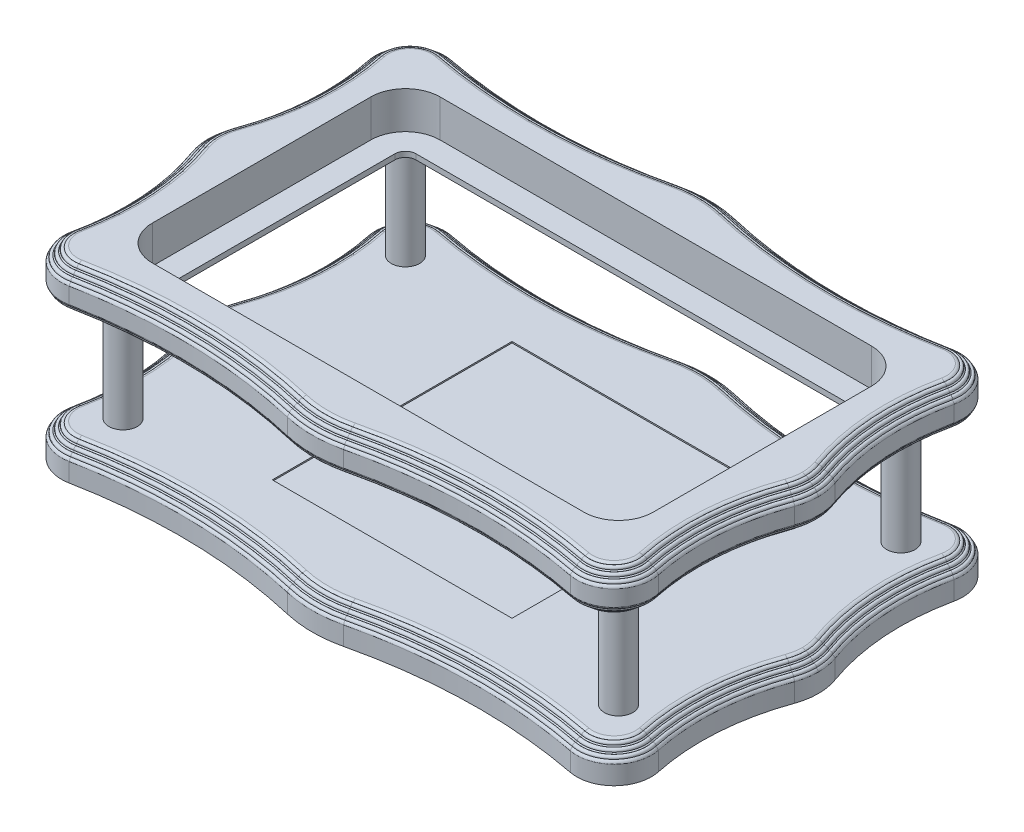
SolidWorks part; units mm, degrees
ref_plane "Front Plane" through (0, 0, 0) normal (0, 0, 1) x (1, 0, 0)
ref_plane "Top Plane" through (0, 0, 0) normal (0, 1, 0) x (1, 0, 0)
ref_plane "Right Plane" through (0, 0, 0) normal (1, 0, 0) x (0, 0, -1)
sketch "Sketch1" plane through (0, 0, 0) normal (0, 1, 0) x (1, 0, 0)
  line L0 (0, 22.5) -> (0, 30.5) construction
  line L1 (50.5, -30.5) -> (-50.5, -30.5) construction
  line L2 (50.5, -30.5) -> (50.5, 30.5) construction
  line L3 (50.5, 30.5) -> (-50.5, 30.5) construction
  line L4 (-50.5, -30.5) -> (-50.5, 30.5) construction
  line L5 (50.5, -30.5) -> (-50.5, 30.5) construction
  line L6 (50.5, 30.5) -> (-50.5, -30.5) construction
  line L7 (-42.5, 22.5) -> (42.5, 22.5) construction
  line L8 (-42.5, 22.5) -> (-42.5, -22.5) construction
  line L9 (-42.5, -22.5) -> (42.5, -22.5) construction
  line L10 (42.5, 22.5) -> (42.5, -22.5) construction
  line L11 (-42.5, 22.5) -> (42.5, -22.5) construction
  line L12 (-42.5, -22.5) -> (42.5, 22.5) construction
  line L13 (42.5, 0) -> (50.5, 0) construction
  line L14 (57.5, 0) -> (50.5, 0) construction
  line L19 (-46.5, 26.5) -> (46.5, 26.5) construction
  line L20 (-46.5, 26.5) -> (-46.5, -26.5) construction
  line L21 (-46.5, -26.5) -> (46.5, -26.5) construction
  line L22 (46.5, 26.5) -> (46.5, -26.5) construction
  line L23 (-46.5, 26.5) -> (46.5, -26.5) construction
  line L24 (-46.5, -26.5) -> (46.5, 26.5) construction
  line L25 (-57.5, 37.5) -> (57.5, 37.5)
  line L26 (-57.5, 37.5) -> (-57.5, -37.5)
  line L27 (-57.5, -37.5) -> (57.5, -37.5)
  line L28 (57.5, 37.5) -> (57.5, -37.5)
  line L29 (-57.5, 37.5) -> (57.5, -37.5) construction
  line L30 (-57.5, -37.5) -> (57.5, 37.5) construction
  line L31 (0, 30.5) -> (0, 37.5) construction
  circle A0 centre (46.5, 26.5) radius 2.6667 construction
  circle A1 centre (-46.5, 26.5) radius 2.6667 construction
  circle A2 centre (46.5, -26.5) radius 2.6667 construction
  circle A3 centre (-46.5, -26.5) radius 2.6667 construction
  point P0 (0, 0)
  point P6 (0, 0)
  point P17 (0, 0)
  point P24 (0, 0)
  point P29 (46.5, 0)
  point P30 (0, 26.5)
  dimension "D5" = 5.3333
  dimension "D1" = 85
  dimension "D2" = 45
  dimension "D3" = 8
  dimension "D4" = 7
extrude "Base" add sketch "Sketch1" along normal blind 6
sketch "Path" plane through (0, 6, 0) normal (0, 1, 0) x (1, 0, 0)
  line L0 (51.25, 0) -> (50.5, 0) construction
  line L1 (28.0361, 31.25) -> (28.0361, 30.5) construction
  line L2 (-4.5909, 34.5) -> (4.5909, 34.5) construction
  line L3 (-54.5, 4.5909) -> (-54.5, -4.5909) construction
  line L4 (-50.5, -30.5) -> (-50.5, 30.5) construction
  line L5 (-50.5, 30.5) -> (50.5, 30.5) construction
  line L6 (-57.5, 37.5) -> (-57.5, -37.5) construction
  line L7 (57.5, 37.5) -> (-57.5, 37.5) construction
  line L8 (0, 34.5) -> (0, 37.5) construction
  line L9 (-54.5, 0) -> (-57.5, 0) construction
  line L10 (0, 0) -> (-50.5, 30.5) construction
  line L11 (-51.25, 31.25) -> (-51.25, -31.25) construction
  line L12 (-51.25, 31.25) -> (51.25, 31.25) construction
  line L13 (-50.5, 0) -> (-41.3182, 0) construction
  line L14 (-41.3182, 0) -> (-32.1364, 0) construction
  line L15 (-32.1364, 0) -> (-22.9545, 0) construction
  line L16 (-22.9545, 0) -> (-13.7727, 0) construction
  line L17 (-13.7727, 0) -> (-4.5909, 0) construction
  line L18 (-4.5909, 0) -> (4.5909, 0) construction
  line L19 (-4.5909, 33.9678) -> (4.5909, 33.9678) construction
  line L20 (-28.0361, 30.5) -> (-28.0361, 24.9545) construction
  line L21 (-28.0361, 24.9545) -> (-28.0361, 19.4091) construction
  line L22 (-28.0361, 19.4091) -> (-28.0361, 13.8636) construction
  line L23 (-28.0361, 13.8636) -> (-28.0361, 8.3182) construction
  line L24 (-28.0361, 8.3182) -> (-28.0361, 2.7727) construction
  line L25 (-28.0361, 2.7727) -> (-28.0361, -2.7727) construction
  line L26 (-54.0165, 2.7727) -> (-54.0165, -2.7727) construction
  line L27 (0, 37.5) -> (0, 46.6818) construction
  line L28 (-57.5, 0) -> (-66.6818, 0) construction
  line L29 (-28.0361, 31.25) -> (-28.0361, 30.5) construction
  line L30 (-51.25, 0) -> (-50.5, 0) construction
  line L31 (54.0165, 2.7727) -> (54.0165, -2.7727) construction
  line L32 (28.0361, 2.7727) -> (28.0361, -2.7727) construction
  line L33 (28.0361, 8.3182) -> (28.0361, 2.7727) construction
  line L34 (28.0361, 13.8636) -> (28.0361, 8.3182) construction
  line L35 (28.0361, 19.4091) -> (28.0361, 13.8636) construction
  line L36 (28.0361, 24.9545) -> (28.0361, 19.4091) construction
  line L37 (28.0361, 30.5) -> (28.0361, 24.9545) construction
  line L38 (13.7727, 0) -> (4.5909, 0) construction
  line L39 (22.9545, 0) -> (13.7727, 0) construction
  line L40 (32.1364, 0) -> (22.9545, 0) construction
  line L41 (41.3182, 0) -> (32.1364, 0) construction
  line L42 (50.5, 0) -> (41.3182, 0) construction
  line L43 (51.25, 31.25) -> (51.25, -31.25) construction
  line L44 (0, 0) -> (50.5, 30.5) construction
  line L45 (54.5, 0) -> (57.5, 0) construction
  line L46 (50.5, -30.5) -> (50.5, 30.5) construction
  line L47 (54.5, 4.5909) -> (54.5, -4.5909) construction
  line L48 (0, 0) -> (50.5, -30.5) construction
  line L49 (50.5, 0) -> (41.3182, 0) construction
  line L50 (41.3182, 0) -> (32.1364, 0) construction
  line L51 (32.1364, 0) -> (22.9545, 0) construction
  line L52 (22.9545, 0) -> (13.7727, 0) construction
  line L53 (13.7727, 0) -> (4.5909, 0) construction
  line L54 (28.0361, -30.5) -> (28.0361, -24.9545) construction
  line L55 (28.0361, -24.9545) -> (28.0361, -19.4091) construction
  line L56 (28.0361, -19.4091) -> (28.0361, -13.8636) construction
  line L57 (28.0361, -13.8636) -> (28.0361, -8.3182) construction
  line L58 (28.0361, -8.3182) -> (28.0361, -2.7727) construction
  line L59 (-51.25, 0) -> (-50.5, 0) construction
  line L60 (-28.0361, -31.25) -> (-28.0361, -30.5) construction
  line L61 (0, -37.5) -> (0, -46.6818) construction
  line L62 (-28.0361, -8.3182) -> (-28.0361, -2.7727) construction
  line L63 (-28.0361, -13.8636) -> (-28.0361, -8.3182) construction
  line L64 (-28.0361, -19.4091) -> (-28.0361, -13.8636) construction
  line L65 (-28.0361, -24.9545) -> (-28.0361, -19.4091) construction
  line L66 (-28.0361, -30.5) -> (-28.0361, -24.9545) construction
  line L67 (-4.5909, -33.9678) -> (4.5909, -33.9678) construction
  line L68 (-4.5909, 0) -> (4.5909, 0) construction
  line L69 (-13.7727, 0) -> (-4.5909, 0) construction
  line L70 (-22.9545, 0) -> (-13.7727, 0) construction
  line L71 (-32.1364, 0) -> (-22.9545, 0) construction
  line L72 (-41.3182, 0) -> (-32.1364, 0) construction
  line L73 (-50.5, 0) -> (-41.3182, 0) construction
  line L74 (-51.25, -31.25) -> (51.25, -31.25) construction
  line L75 (0, 0) -> (-50.5, -30.5) construction
  line L76 (0, -34.5) -> (0, -37.5) construction
  line L77 (-50.5, -30.5) -> (50.5, -30.5) construction
  line L78 (-4.5909, -34.5) -> (4.5909, -34.5) construction
  line L79 (28.0361, -31.25) -> (28.0361, -30.5) construction
  line L80 (51.25, 0) -> (50.5, 0) construction
  arc A0 (4.5909, 33.9678) -> (-4.5909, 33.9678) centre (0, 14.4322) ccw
  arc A1 (-54.0165, -2.7727) -> (-54.0165, 2.7727) centre (-46.3077, 0) cw
  circle A2 centre (-48.36, 29.2075) radius 4 construction
  arc A3 (-54.0165, 2.7727) -> (-52.2727, 28.3765) centre (-98.1256, 18.6381) ccw
  arc A4 (-4.5909, 33.9678) -> (-47.5966, 33.134) centre (-28.0361, 133.734) cw
  arc A5 (-52.2727, 28.3765) -> (-47.5966, 33.134) centre (-48.36, 29.2075) cw
  circle A6 centre (48.36, 29.2075) radius 4 construction
  arc A7 (52.2727, 28.3765) -> (47.5966, 33.134) centre (48.36, 29.2075) ccw
  arc A8 (4.5909, 33.9678) -> (47.5966, 33.134) centre (28.0361, 133.734) ccw
  arc A9 (54.0165, 2.7727) -> (52.2727, 28.3765) centre (98.1256, 18.6381) cw
  arc A10 (54.0165, -2.7727) -> (54.0165, 2.7727) centre (46.3077, 0) ccw
  circle A11 centre (48.36, -29.2075) radius 4 construction
  circle A12 centre (-48.36, -29.2075) radius 4 construction
  arc A13 (54.0165, -2.7727) -> (52.2727, -28.3765) centre (98.1256, -18.6381) ccw
  arc A14 (4.5909, -33.9678) -> (47.5966, -33.134) centre (28.0361, -133.734) cw
  arc A15 (52.2727, -28.3765) -> (47.5966, -33.134) centre (48.36, -29.2075) cw
  arc A16 (-52.2727, -28.3765) -> (-47.5966, -33.134) centre (-48.36, -29.2075) ccw
  arc A17 (-4.5909, -33.9678) -> (-47.5966, -33.134) centre (-28.0361, -133.734) ccw
  arc A18 (-54.0165, -2.7727) -> (-52.2727, -28.3765) centre (-98.1256, -18.6381) cw
  arc A19 (4.5909, -33.9678) -> (-4.5909, -33.9678) centre (0, -14.4322) cw
  point P37 (-50.5, 0)
  point P46 (0, 0)
  point P72 (0, 33.9678)
  point P73 (0, 0)
  point P78 (0, 31.25)
  point P82 (0, 30.5)
  point P96 (50.5, 0)
  point P97 (51.25, 0)
  point P109 (28.0361, 0)
  point P110 (54.0165, 0)
  point P117 (-54.0165, 0)
  point P118 (-28.0361, 0)
  point P130 (-51.25, 0)
  point P132 (-50.5, 0)
  point P146 (0, -30.5)
  point P147 (0, -31.25)
  point P148 (0, 0)
  point P149 (0, -33.9678)
  dimension "D5" = 8
  dimension "D1" = 7
  dimension "D2" = 7
  dimension "D3" = 3
  dimension "D4" = 2.5
  dimension "D7" = 0.75
sketch "Profile" plane through (0, 0, 0) normal (0, 0, 1) x (1, 0, 0)
  line L0 (54.5, 6) -> (57.5, 6)
  line L1 (57.5, 6) -> (57.5, 3.5) construction
  line L2 (57.5, 6) -> (55.25, 5.375) construction
  line L3 (57.5, 6) -> (56, 4.75) construction
  line L4 (57.5, 6) -> (56.75, 4.125) construction
  line L5 (55.25, 5.375) -> (54.5, 6) construction
  line L6 (55.25, 5.375) -> (56, 4.75) construction
  line L7 (56, 4.75) -> (56.75, 4.125) construction
  line L8 (56.75, 4.125) -> (57.5, 3.5) construction
  line L9 (56, 4.75) -> (57.5, 4.75) construction
  line L10 (56.75, 4.125) -> (57.5, 4.125) construction
  line L11 (55.25, 5.375) -> (57.5, 5.375) construction
  line L12 (57.5, 6) -> (67.5, 8)
  line L13 (67.5, 8) -> (67.5, 3.5)
  line L15 (57.5, 3.5) -> (57.5, -4.5)
  line L16 (57.5, -4.5) -> (67.5, -4.5)
  line L17 (57.5, 3.5) -> (67.5, 3.5) construction
  line L18 (67.5, -4.5) -> (67.5, 3.5)
  circle A0 centre (55.25, 5.375) radius 0.39 construction
  circle A1 centre (56, 4.75) radius 0.39 construction
  circle A2 centre (56.75, 4.125) radius 0.39 construction
  arc A3 (56.75, 4.125) -> (57.5, 3.5) centre (56.75, 3.3625) cw construction
  arc A4 (56, 4.75) -> (56.75, 4.125) centre (56, 3.9875) cw construction
  arc A5 (55.25, 5.375) -> (56, 4.75) centre (55.25, 4.6125) cw construction
  arc A6 (54.5, 6) -> (55.25, 5.375) centre (54.5, 5.2375) cw construction
  arc A7 (54.5, 6) -> (55.0839, 5.7279) centre (54.5, 5.2375) cw
  arc A8 (55.0839, 5.7279) -> (55.627, 5.2753) centre (55.25, 5.375) cw
  arc A9 (55.627, 5.2753) -> (55.8339, 5.1029) centre (55.25, 4.6125) cw
  arc A10 (55.8339, 5.1029) -> (56.377, 4.6503) centre (56, 4.75) cw
  arc A11 (56.377, 4.6503) -> (56.5839, 4.4779) centre (56, 3.9875) cw
  arc A12 (56.5839, 4.4779) -> (57.127, 4.0253) centre (56.75, 4.125) cw
  arc A13 (57.127, 4.0253) -> (57.5, 3.5) centre (56.75, 3.3625) cw
  dimension "D3" = 0.78
  dimension "D1" = 3
  dimension "D2" = 2.5
  dimension "D4" = 10
  dimension "D5" = 8
sweep "Sweep Cut" cut profiles "Profile" path "Path"
sketch "Sketch4" plane through (0, 6, 0) normal (0, 1, 0) x (1, 0, 0)
  circle A0 centre (-46.5, -26.5) radius 2.6667 construction
  circle A1 centre (46.5, -26.5) radius 2.6667 construction
  circle A2 centre (46.5, 26.5) radius 2.6667 construction
  circle A3 centre (-46.5, 26.5) radius 2.6667 construction
  circle A4 centre (-46.5, -26.5) radius 2.6667
  circle A5 centre (46.5, -26.5) radius 2.6667
  circle A6 centre (46.5, 26.5) radius 2.6667
  circle A7 centre (-46.5, 26.5) radius 2.6667
extrude "Support Posts" add sketch "Sketch4" along normal blind 20.5
sketch "Sketch5" plane through (0, 6, 0) normal (0, 1, 0) x (1, 0, 0)
  line L1 (22.5, -22.5) -> (-22.5, -22.5)
  line L2 (22.5, -22.5) -> (22.5, 22.5)
  line L3 (22.5, 22.5) -> (-22.5, 22.5)
  line L4 (-22.5, -22.5) -> (-22.5, 22.5)
  line L5 (22.5, -22.5) -> (-22.5, 22.5) construction
  line L6 (22.5, 22.5) -> (-22.5, -22.5) construction
  point P0 (0, 0)
  dimension "D1" = 45
extrude "Pyramid Base Cut" cut sketch "Sketch5" against normal blind 0.25
sketch "Sketch6" plane through (0, 26.5, 0) normal (0, 1, 0) x (1, 0, 0)
  line L0 (-57.5, 37.5) -> (57.5, 37.5) construction
  line L1 (57.5, 37.5) -> (57.5, -37.5) construction
  line L2 (-57.5, -37.5) -> (57.5, -37.5) construction
  line L3 (-57.5, 37.5) -> (-57.5, -37.5) construction
  line L4 (-57.5, 37.5) -> (57.5, 37.5)
  line L5 (57.5, 37.5) -> (57.5, -37.5)
  line L6 (-57.5, -37.5) -> (57.5, -37.5)
  line L7 (-57.5, 37.5) -> (-57.5, -37.5)
extrude "Boss-Extrude2" add sketch "Sketch6" along normal blind 8
sketch "Path 2" plane through (0, 26.5, 0) normal (0, -1, 0) x (1, 0, 0)
  arc A16 (52.2727, 28.3765) -> (54.0165, 2.7727) centre (98.1256, 18.6381) ccw
  arc A17 (54.0165, -2.7727) -> (54.0165, 2.7727) centre (46.3077, 0) ccw
  arc A18 (54.0165, -2.7727) -> (52.2727, -28.3765) centre (98.1256, -18.6381) ccw
  arc A19 (47.5966, -33.134) -> (52.2727, -28.3765) centre (48.36, -29.2075) ccw
  arc A20 (47.5966, -33.134) -> (4.5909, -33.9678) centre (28.0361, -133.734) ccw
  arc A21 (-4.5909, -33.9678) -> (4.5909, -33.9678) centre (0, -14.4322) ccw
  arc A22 (-4.5909, -33.9678) -> (-47.5966, -33.134) centre (-28.0361, -133.734) ccw
  arc A23 (-52.2727, -28.3765) -> (-47.5966, -33.134) centre (-48.36, -29.2075) ccw
  arc A24 (-52.2727, -28.3765) -> (-54.0165, -2.7727) centre (-98.1256, -18.6381) ccw
  arc A25 (-54.0165, 2.7727) -> (-54.0165, -2.7727) centre (-46.3077, 0) ccw
  arc A26 (-54.0165, 2.7727) -> (-52.2727, 28.3765) centre (-98.1256, 18.6381) ccw
  arc A27 (-47.5966, 33.134) -> (-52.2727, 28.3765) centre (-48.36, 29.2075) ccw
  arc A28 (-47.5966, 33.134) -> (-4.5909, 33.9678) centre (-28.0361, 133.734) ccw
  arc A29 (4.5909, 33.9678) -> (-4.5909, 33.9678) centre (0, 14.4322) ccw
  arc A30 (4.5909, 33.9678) -> (47.5966, 33.134) centre (28.0361, 133.734) ccw
  arc A31 (52.2727, 28.3765) -> (47.5966, 33.134) centre (48.36, 29.2075) ccw
  arc A32 (52.2727, 28.3765) -> (54.0165, 2.7727) centre (98.1256, 18.6381) ccw
  arc A33 (54.0165, -2.7727) -> (54.0165, 2.7727) centre (46.3077, 0) ccw
  arc A34 (54.0165, -2.7727) -> (52.2727, -28.3765) centre (98.1256, -18.6381) ccw
  arc A35 (47.5966, -33.134) -> (52.2727, -28.3765) centre (48.36, -29.2075) ccw
  arc A36 (47.5966, -33.134) -> (4.5909, -33.9678) centre (28.0361, -133.734) ccw
  arc A37 (-4.5909, -33.9678) -> (4.5909, -33.9678) centre (0, -14.4322) ccw
  arc A38 (-4.5909, -33.9678) -> (-47.5966, -33.134) centre (-28.0361, -133.734) ccw
  arc A39 (-52.2727, -28.3765) -> (-47.5966, -33.134) centre (-48.36, -29.2075) ccw
  arc A40 (-52.2727, -28.3765) -> (-54.0165, -2.7727) centre (-98.1256, -18.6381) ccw
  arc A41 (-54.0165, 2.7727) -> (-54.0165, -2.7727) centre (-46.3077, 0) ccw
  arc A42 (-54.0165, 2.7727) -> (-52.2727, 28.3765) centre (-98.1256, 18.6381) ccw
  arc A43 (-47.5966, 33.134) -> (-52.2727, 28.3765) centre (-48.36, 29.2075) ccw
  arc A44 (-47.5966, 33.134) -> (-4.5909, 33.9678) centre (-28.0361, 133.734) ccw
  arc A45 (4.5909, 33.9678) -> (-4.5909, 33.9678) centre (0, 14.4322) ccw
  arc A46 (4.5909, 33.9678) -> (47.5966, 33.134) centre (28.0361, 133.734) ccw
  arc A47 (52.2727, 28.3765) -> (47.5966, 33.134) centre (48.36, 29.2075) ccw
  dimension "D1" = 0
sketch "Profile 2" plane through (0, 0, 0) normal (0, 0, 1) x (1, 0, 0)
  line L0 (54.5, 34.5) -> (57.5, 34.5)
  line L1 (57.5, 34.5) -> (57.5, 32) construction
  line L2 (57.5, 34.5) -> (55.25, 33.875) construction
  line L3 (57.5, 34.5) -> (56, 33.25) construction
  line L4 (57.5, 34.5) -> (56.75, 32.625) construction
  line L5 (55.25, 33.875) -> (54.5, 34.5) construction
  line L6 (55.25, 33.875) -> (56, 33.25) construction
  line L7 (56, 33.25) -> (56.75, 32.625) construction
  line L8 (56.75, 32.625) -> (57.5, 32) construction
  line L9 (56, 33.25) -> (57.5, 33.25) construction
  line L10 (56.75, 32.625) -> (57.5, 32.625) construction
  line L11 (55.25, 33.875) -> (57.5, 33.875) construction
  line L12 (57.5, 34.5) -> (67.5, 34.5)
  line L13 (67.5, 34.5) -> (67.5, 32)
  line L14 (57.5, 32) -> (57.5, 29)
  line L15 (57.5, 30.5) -> (67.5, 30.5) construction
  line L16 (57.5, 32) -> (67.5, 32) construction
  line L17 (67.5, 29) -> (67.5, 32)
  line L18 (67.5, 30.5) -> (70, 30.5) construction
  line L19 (57.5, 29) -> (67.5, 29) construction
  line L20 (55.25, 27.125) -> (57.5, 27.125) construction
  line L21 (56.75, 28.375) -> (57.5, 28.375) construction
  line L22 (56, 27.75) -> (57.5, 27.75) construction
  line L23 (56.75, 28.375) -> (57.5, 29) construction
  line L24 (56, 27.75) -> (56.75, 28.375) construction
  line L25 (55.25, 27.125) -> (56, 27.75) construction
  line L26 (55.25, 27.125) -> (54.5, 26.5) construction
  line L27 (57.5, 26.5) -> (56.75, 28.375) construction
  line L28 (57.5, 26.5) -> (56, 27.75) construction
  line L29 (57.5, 26.5) -> (55.25, 27.125) construction
  line L30 (57.5, 26.5) -> (57.5, 29) construction
  line L31 (67.5, 26.5) -> (67.5, 29)
  line L32 (57.5, 26.5) -> (67.5, 26.5)
  line L33 (54.5, 26.5) -> (57.5, 26.5)
  line L39 (-57.5, 34.5) -> (57.5, 34.5) construction
  circle A0 centre (55.25, 33.875) radius 0.39 construction
  circle A1 centre (56, 33.25) radius 0.39 construction
  circle A2 centre (56.75, 32.625) radius 0.39 construction
  arc A3 (56.75, 32.625) -> (57.5, 32) centre (56.75, 31.8625) cw construction
  arc A4 (56, 33.25) -> (56.75, 32.625) centre (56, 32.4875) cw construction
  arc A5 (55.25, 33.875) -> (56, 33.25) centre (55.25, 33.1125) cw construction
  arc A6 (54.5, 34.5) -> (55.25, 33.875) centre (54.5, 33.7375) cw construction
  arc A7 (54.5, 34.5) -> (55.0839, 34.2279) centre (54.5, 33.7375) cw
  arc A8 (55.0839, 34.2279) -> (55.627, 33.7753) centre (55.25, 33.875) cw
  arc A9 (55.627, 33.7753) -> (55.8339, 33.6029) centre (55.25, 33.1125) cw
  arc A10 (55.8339, 33.6029) -> (56.377, 33.1503) centre (56, 33.25) cw
  arc A11 (56.377, 33.1503) -> (56.5839, 32.9779) centre (56, 32.4875) cw
  arc A12 (56.5839, 32.9779) -> (57.127, 32.5253) centre (56.75, 32.625) cw
  arc A13 (57.127, 32.5253) -> (57.5, 32) centre (56.75, 31.8625) cw
  arc A14 (54.5, 26.5) -> (55.25, 27.125) centre (54.5, 27.2625) ccw construction
  arc A15 (55.25, 27.125) -> (56, 27.75) centre (55.25, 27.8875) ccw construction
  arc A16 (56, 27.75) -> (56.75, 28.375) centre (56, 28.5125) ccw construction
  arc A17 (56.75, 28.375) -> (57.5, 29) centre (56.75, 29.1375) ccw construction
  circle A18 centre (56.75, 28.375) radius 0.39 construction
  circle A19 centre (56, 27.75) radius 0.39 construction
  circle A20 centre (55.25, 27.125) radius 0.39 construction
  arc A21 (57.127, 28.4747) -> (57.5, 29) centre (56.75, 29.1375) ccw
  arc A22 (56.5839, 28.0221) -> (57.127, 28.4747) centre (56.75, 28.375) ccw
  arc A23 (56.377, 27.8497) -> (56.5839, 28.0221) centre (56, 28.5125) ccw
  arc A24 (55.8339, 27.3971) -> (56.377, 27.8497) centre (56, 27.75) ccw
  arc A25 (55.627, 27.2247) -> (55.8339, 27.3971) centre (55.25, 27.8875) ccw
  arc A26 (55.0839, 26.7721) -> (55.627, 27.2247) centre (55.25, 27.125) ccw
  arc A27 (54.5, 26.5) -> (55.0839, 26.7721) centre (54.5, 27.2625) ccw
  point P59 (0, 0)
  point P60 (0, 0)
  dimension "D3" = 0.78
  dimension "D1" = 3
  dimension "D2" = 2.5
  dimension "D4" = 10
sweep "Sweep Cut 2" cut profiles "Profile 2" path "Path 2"
sketch "Sketch10" plane through (0, 34.5, 0) normal (0, 1, 0) x (1, 0, 0)
  line L1 (40.5, -22.5) -> (-40.5, -22.5)
  line L2 (42.5, -20.5) -> (42.5, 20.5)
  line L3 (40.5, 22.5) -> (-40.5, 22.5)
  line L4 (-42.5, -20.5) -> (-42.5, 20.5)
  line L5 (42.5, -22.5) -> (-42.5, 22.5) construction
  line L6 (42.5, 22.5) -> (-42.5, -22.5) construction
  arc A0 (-40.5, -22.5) -> (-42.5, -20.5) centre (-40.5, -20.5) cw
  arc A1 (40.5, -22.5) -> (42.5, -20.5) centre (40.5, -20.5) ccw
  arc A2 (42.5, 20.5) -> (40.5, 22.5) centre (40.5, 20.5) ccw
  arc A3 (-40.5, 22.5) -> (-42.5, 20.5) centre (-40.5, 20.5) ccw
  point P0 (0, 0)
  dimension "D1" = 2
  dimension "D2" = 85
  dimension "D3" = 45
extrude "Screen Size Cut" cut sketch "Sketch10" against normal up to surface (8 mm away) up to face at (-46.5, 26.5, -23.8333)
sketch "Sketch12" plane through (0, 34.5, 0) normal (0, 1, 0) x (1, 0, 0)
  line L0 (47, -20.5) -> (47, 20.5)
  line L1 (40.5, 27) -> (-40.5, 27)
  line L2 (-47, 20.5) -> (-47, -20.5)
  line L3 (-40.5, -27) -> (40.5, -27)
  line L4 (-42.5, 20.5) -> (-42.5, -20.5)
  line L5 (-40.5, -22.5) -> (40.5, -22.5)
  line L6 (42.5, -20.5) -> (42.5, 20.5)
  line L7 (40.5, 22.5) -> (-40.5, 22.5)
  line L8 (-42.5, 20.5) -> (-42.5, -20.5) construction
  line L9 (-40.5, -22.5) -> (40.5, -22.5) construction
  line L10 (42.5, -20.5) -> (42.5, 20.5) construction
  line L11 (40.5, 22.5) -> (-40.5, 22.5) construction
  arc A0 (47, 20.5) -> (40.5, 27) centre (40.5, 20.5) ccw
  arc A1 (-40.5, 27) -> (-47, 20.5) centre (-40.5, 20.5) ccw
  arc A2 (-47, -20.5) -> (-40.5, -27) centre (-40.5, -20.5) ccw
  arc A3 (40.5, -27) -> (47, -20.5) centre (40.5, -20.5) ccw
  arc A4 (-42.5, -20.5) -> (-40.5, -22.5) centre (-40.5, -20.5) ccw
  arc A5 (40.5, -22.5) -> (42.5, -20.5) centre (40.5, -20.5) ccw
  arc A6 (42.5, 20.5) -> (40.5, 22.5) centre (40.5, 20.5) ccw
  arc A7 (-40.5, 22.5) -> (-42.5, 20.5) centre (-40.5, 20.5) ccw
  arc A8 (-42.5, -20.5) -> (-40.5, -22.5) centre (-40.5, -20.5) ccw construction
  arc A9 (40.5, -22.5) -> (42.5, -20.5) centre (40.5, -20.5) ccw construction
  arc A10 (42.5, 20.5) -> (40.5, 22.5) centre (40.5, 20.5) ccw construction
  arc A11 (-40.5, 22.5) -> (-42.5, 20.5) centre (-40.5, 20.5) ccw construction
  arc A17 (54.0165, -2.7727) -> (52.2727, -28.3765) centre (98.1256, -18.6381) ccw
  arc A18 (54.0165, -2.7727) -> (54.5, 0) centre (46.3077, 0) ccw
  arc A19 (54.5, 0) -> (54.0165, 2.7727) centre (46.3077, 0) ccw
  arc A20 (52.2727, 28.3765) -> (54.0165, 2.7727) centre (98.1256, 18.6381) ccw
  arc A21 (52.2727, 28.3765) -> (47.5966, 33.134) centre (48.36, 29.2075) ccw
  arc A22 (4.5909, 33.9678) -> (47.5966, 33.134) centre (28.0361, 133.734) ccw
  arc A23 (4.5909, 33.9678) -> (-4.5909, 33.9678) centre (0, 14.4322) ccw
  arc A24 (-47.5966, 33.134) -> (-4.5909, 33.9678) centre (-28.0361, 133.734) ccw
  arc A25 (-47.5966, 33.134) -> (-52.2727, 28.3765) centre (-48.36, 29.2075) ccw
  arc A26 (-54.0165, 2.7727) -> (-52.2727, 28.3765) centre (-98.1256, 18.6381) ccw
  arc A27 (-54.0165, 2.7727) -> (-54.0165, -2.7727) centre (-46.3077, 0) ccw
  arc A28 (-52.2727, -28.3765) -> (-54.0165, -2.7727) centre (-98.1256, -18.6381) ccw
  arc A29 (-52.2727, -28.3765) -> (-47.5966, -33.134) centre (-48.36, -29.2075) ccw
  arc A30 (-4.5909, -33.9678) -> (-47.5966, -33.134) centre (-28.0361, -133.734) ccw
  arc A31 (-4.5909, -33.9678) -> (4.5909, -33.9678) centre (0, -14.4322) ccw
  arc A32 (47.5966, -33.134) -> (4.5909, -33.9678) centre (28.0361, -133.734) ccw
  arc A33 (47.5966, -33.134) -> (52.2727, -28.3765) centre (48.36, -29.2075) ccw
  arc A34 (54.0165, -2.7727) -> (52.2727, -28.3765) centre (98.1256, -18.6381) ccw
  arc A35 (54.0165, -2.7727) -> (54.5, 0) centre (46.3077, 0) ccw
  arc A36 (54.5, 0) -> (54.0165, 2.7727) centre (46.3077, 0) ccw
  arc A37 (52.2727, 28.3765) -> (54.0165, 2.7727) centre (98.1256, 18.6381) ccw
  arc A38 (52.2727, 28.3765) -> (47.5966, 33.134) centre (48.36, 29.2075) ccw
  arc A39 (4.5909, 33.9678) -> (47.5966, 33.134) centre (28.0361, 133.734) ccw
  arc A40 (4.5909, 33.9678) -> (-4.5909, 33.9678) centre (0, 14.4322) ccw
  arc A41 (-47.5966, 33.134) -> (-4.5909, 33.9678) centre (-28.0361, 133.734) ccw
  arc A42 (-47.5966, 33.134) -> (-52.2727, 28.3765) centre (-48.36, 29.2075) ccw
  arc A43 (-54.0165, 2.7727) -> (-52.2727, 28.3765) centre (-98.1256, 18.6381) ccw
  arc A44 (-54.0165, 2.7727) -> (-54.0165, -2.7727) centre (-46.3077, 0) ccw
  arc A45 (-52.2727, -28.3765) -> (-54.0165, -2.7727) centre (-98.1256, -18.6381) ccw
  arc A46 (-52.2727, -28.3765) -> (-47.5966, -33.134) centre (-48.36, -29.2075) ccw
  arc A47 (-4.5909, -33.9678) -> (-47.5966, -33.134) centre (-28.0361, -133.734) ccw
  arc A48 (-4.5909, -33.9678) -> (4.5909, -33.9678) centre (0, -14.4322) ccw
  arc A49 (47.5966, -33.134) -> (4.5909, -33.9678) centre (28.0361, -133.734) ccw
  arc A50 (47.5966, -33.134) -> (52.2727, -28.3765) centre (48.36, -29.2075) ccw
  point P58 (0, 0)
  dimension "D1" = 0
  dimension "D2" = 0
  dimension "D3" = 4.5
extrude "Device Shape Cut" cut sketch "Sketch12" against normal offset from surface (7 mm away) 1 contours L0 A0 L1 A1 L2 A2 L3 A3 up to face at (0, 26.5, 0)
equation "\"screen width\"= 45.00mm"
equation "\"screen height\"= 85.00mm"
equation "\"top cutoff\" = 2.00mm"
equation "\"A\" = \"screen width\" / 2"
equation "\"B\" = \"screen width\" / 2"
equation "\"screen hypotenuse\" = sqr ( ( \"A\" * \"A\" ) + ( \"B\" * \"B\" ) )"
equation "\"a2\" = \"top cutoff\" "
equation "\"b2\" = \"top cutoff\""
equation "\"top cutoff hypotenuse\" = sqr ( ( \"a2\" * \"a2\" ) + ( \"b2\" * \"b2\" ) )"
equation "\"total hypotenuse\" = \"screen hypotenuse\" - \"top cutoff hypotenuse\""
equation "\"image display width\" = ( \"A\" / 3 ) * 2"
equation "\"image display height\" = ( \"B\" / 3 ) * 2"
equation "\"D1@Sketch1\"=\"screen height\""
equation "\"D2@Sketch1\"=\"screen width\""
equation "\"D5@Sketch1\"=\"D3@Sketch1\"/1.5"
equation "\"D1@Support Posts\" = \"A\" - \"a2\""
equation "\"D1@Sketch5\"=\"screen width\""
equation "\"D2@Sketch10\"=\"screen height\""
equation "\"D3@Sketch10\"=\"screen width\""
